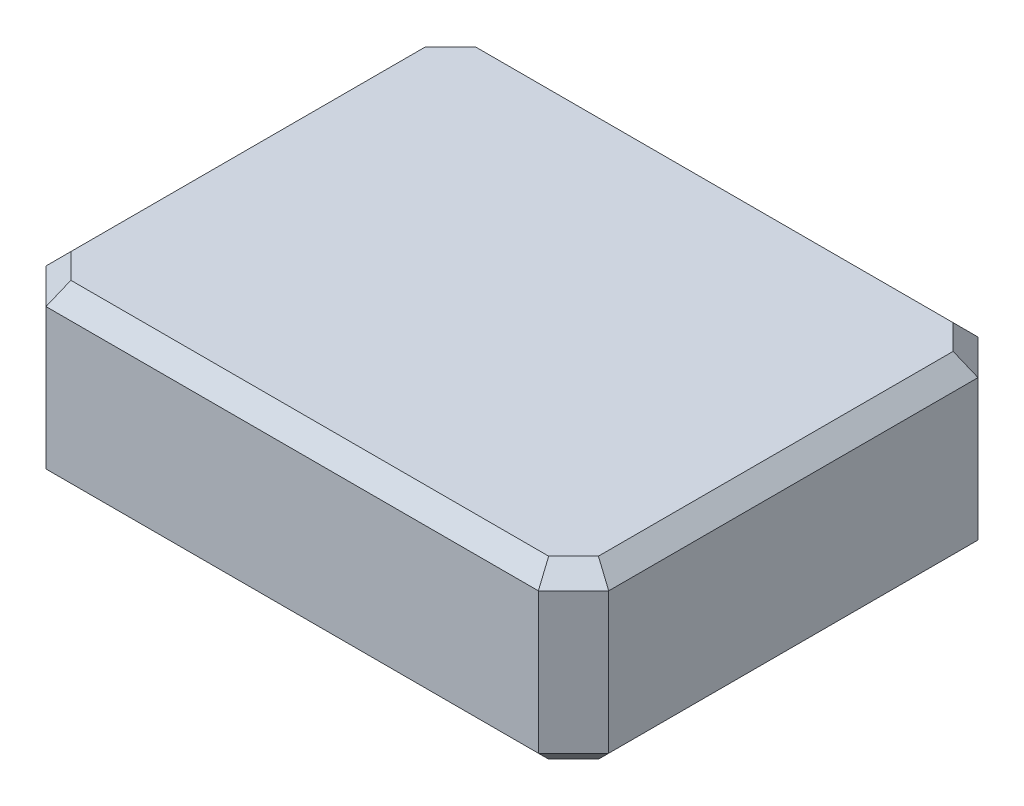
SolidWorks part; units mm, degrees
ref_plane "Front Plane" through (0, 0, 0) normal (0, 0, 1) x (1, 0, 0)
ref_plane "Top Plane" through (0, 0, 0) normal (0, 1, 0) x (1, 0, 0)
ref_plane "Right Plane" through (0, 0, 0) normal (1, 0, 0) x (0, 0, -1)
ref_axis "X" through (-88.99, 0, 0) along (1, 0, 0)
ref_axis "Y" through (0, 55, 0) along (0, -1, 0)
ref_axis "Z" through (0, 0, -88.99) along (0, 0, 1)
sketch "Sketch1" plane through (0, 0, 0) normal (0, 1, 0) x (1, 0, 0)
  line L1 (-160, 125) -> (160, 125)
  line L2 (-160, 125) -> (-160, -125)
  line L3 (-160, -125) -> (160, -125)
  line L4 (160, 125) -> (160, -125)
  line L5 (-160, 125) -> (160, -125) construction
  line L6 (-160, -125) -> (160, 125) construction
  point P0 (0, 0)
  dimension "D1" = 250
  dimension "D2" = 320
extrude "Boss-Extrude1" add sketch "Sketch1" along normal mid plane 100
chamfer "Chamfer1" distance 20 angle 45 4 edges at (-160, 0, -125) (-160, 0, 125) (160, 0, -125) (160, 0, 125)
chamfer "Chamfer2" distance 10 angle 45 16 edges at (150, 50, -115) (160, 50, 0) (150, 50, 115) (0, 50, 125) (-150, 50, 115) (-160, 50, 0) (-150, 50, -115) (0, 50, -125) (-150, -50, 115) (0, -50, 125) (150, -50, 115) (160, -50, 0) (150, -50, -115) (0, -50, -125) (-150, -50, -115) (-160, -50, 0)
